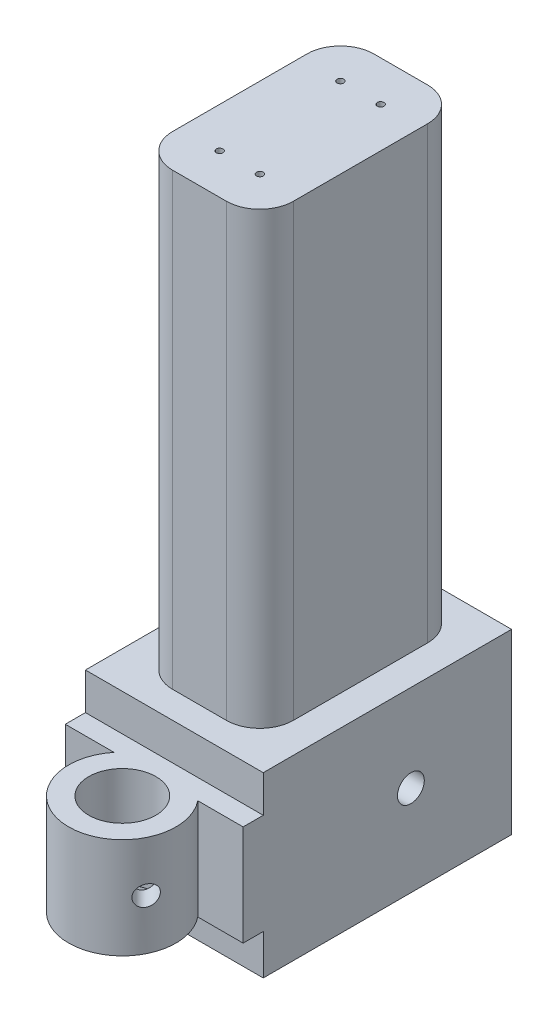
SolidWorks part; units mm, degrees
ref_plane "Plan de face" through (0, 0, 0) normal (0, 0, 1) x (1, 0, 0)
ref_plane "Plan de dessus" through (0, 0, 0) normal (0, 1, 0) x (1, 0, 0)
ref_plane "Plan de droite" through (0, 0, 0) normal (1, 0, 0) x (0, 0, -1)
sketch "Esquisse1" plane through (0, 0, 0) normal (0, 0, 1) x (1, 0, 0)
  line L1 (-12.6964, 11.5945) -> (13.8036, 11.5945)
  line L2 (-12.6964, 11.5945) -> (-12.6964, -14.9055)
  line L3 (-12.6964, -14.9055) -> (13.8036, -14.9055)
  line L4 (13.8036, 11.5945) -> (13.8036, -14.9055)
  dimension "D1" = 26.5
  dimension "D2" = 26.5
extrude "Boss.-Extru.1" add sketch "Esquisse1" along normal blind 40
sketch "Esquisse2" plane through (0, 0, 0) normal (0, 0, -1) x (-1, 0, 0)
  line L0 (-13.8036, -14.9055) -> (-13.8036, 11.5945) construction
  line L1 (-10.8036, 8.5945) -> (9.6964, 8.5945)
  line L2 (-10.8036, 8.5945) -> (-10.8036, -11.9055)
  line L3 (-10.8036, -11.9055) -> (9.6964, -11.9055)
  line L4 (9.6964, 8.5945) -> (9.6964, -11.9055)
  line L5 (-13.8036, 11.5945) -> (12.6964, 11.5945) construction
  dimension "D1" = 20.5
  dimension "D2" = 20.5
  dimension "D3" = 3
  dimension "D4" = 3
extrude "Enlèv. mat.-Extru.1" cut sketch "Esquisse2" against normal blind 21
ref_plane "Plan1" through (0, -1.4055, 0) normal (0, -1, 0) x (-1, 0, 0)
sketch "Esquisse4" plane through (0, -1.4055, 0) normal (0, -1, 0) x (-1, 0, 0)
  line L0 (12.6964, -40) -> (12.6964, 0) construction
  line L1 (-13.8036, -40) -> (12.6964, -40) construction
  circle A0 centre (-0.8036, -45) radius 5
  circle A1 centre (-0.8036, -45) radius 8
  dimension "D2" = 10
  dimension "D4" = 16
  dimension "D1" = 13.5
  dimension "D3" = 5
extrude "Boss.-Extru.3" add sketch "Esquisse4" along normal blind 7.5
extrude "Boss.-Extru.4" add sketch "Esquisse4<4>" against normal blind 7.5
sketch "Esquisse4<4>" plane through (0, -1.4055, 0) normal (0, -1, 0) x (-1, 0, 0) same geometry as "Esquisse4"
sketch "Esquisse8" plane through (0, -14.9055, 0) normal (0, -1, 0) x (1, 0, 0)
  line L0 (13.8036, 40) -> (13.8036, 0) construction
  line L1 (13.8036, 37) -> (-12.6964, 37)
  line L2 (13.8036, 37) -> (13.8036, 40)
  line L3 (13.8036, 40) -> (-12.6964, 40)
  line L4 (-12.6964, 37) -> (-12.6964, 40)
  dimension "D1" = 3
extrude "Enlèv. mat.-Extru.4" cut sketch "Esquisse8" against normal blind 6
sketch "Esquisse9" plane through (0, 11.5945, 0) normal (0, 1, 0) x (1, 0, 0)
  line L0 (-12.6964, -40) -> (-12.6964, 0) construction
  line L1 (-12.6964, -37) -> (13.8036, -37)
  line L2 (-12.6964, -37) -> (-12.6964, -40)
  line L3 (-12.6964, -40) -> (13.8036, -40)
  line L4 (13.8036, -37) -> (13.8036, -40)
  dimension "D1" = 3
ref_plane "Plan2" through (0, 0, 54) normal (0, 0, 1) x (1, 0, 0)
sketch "Esquisse12" plane through (0, 11.5945, 0) normal (0, 1, 0) x (1, 0, 0)
  line L1 (9.3036, -3) -> (-8.6964, -3)
  line L2 (9.3036, -3) -> (9.3036, -33)
  line L3 (9.3036, -33) -> (-8.6964, -33)
  line L4 (-8.6964, -3) -> (-8.6964, -33)
  line L6 (13.8036, 0) -> (-12.6964, 0) construction
  line L8 (13.8036, -40) -> (13.8036, 0) construction
  dimension "D1" = 18
  dimension "D2" = 30
  dimension "D3" = 3
  dimension "D4" = 4.5
extrude "Boss.-Extru.5" add sketch "Esquisse12" along normal blind 67
fillet "Congé1" radius 5 1 edges at (9.3036, 45.0945, 33) type face fillet first side face at (9.3036, 45.0945, 18) second side face at (0.3036, 45.0945, 33)
fillet "Congé2" radius 5 1 edges at (-8.6964, 45.0945, 33) type face fillet first side face at (-2.1964, 45.0945, 33) second side face at (-8.6964, 45.0945, 18)
fillet "Congé3" radius 5 1 edges at (-8.6964, 45.0945, 3) type face fillet first side face at (-8.6964, 45.0945, 15.5) second side face at (0.3036, 45.0945, 3)
fillet "Congé4" radius 5 1 edges at (9.3036, 45.0945, 3) type face fillet first side face at (9.3036, 45.0945, 15.5) second side face at (2.8036, 45.0945, 3)
sketch "Esquisse13" plane through (0, 78.5945, 0) normal (0, 1, 0) x (1, 0, 0)
  line L0 (4.3036, -3) -> (-3.6964, -3) construction
  line L1 (9.3036, -28) -> (9.3036, -8) construction
  line L2 (4.3036, -3) -> (-3.6964, -3) construction
  line L3 (-8.6964, -8) -> (-8.6964, -28) construction
  line L4 (-3.6964, -33) -> (4.3036, -33) construction
  circle A0 centre (3.3036, -9) radius 0.5
  circle A1 centre (-2.6964, -9) radius 0.5
  circle A2 centre (3.3036, -27) radius 0.5
  circle A3 centre (-2.6964, -27) radius 0.5
  dimension "D1" = 1
  dimension "D2" = 1
  dimension "D3" = 1
  dimension "D4" = 1
  dimension "D5" = 6
  dimension "D6" = 6
  dimension "D7" = 6
  dimension "D8" = 6
  dimension "D9" = 6
  dimension "D10" = 6
  dimension "D11" = 6
  dimension "D12" = 6
ref_plane "Plan13" through (0, 0, 51) normal (0, 0, 1) x (1, 0, 0)
ref_plane "Plan14" through (13.6518, 0, 13.6518) normal (-0.7071, 0, -0.7071) x (-0.7071, 0, 0.7071)
ref_plane "Plan15" through (28.5587, 0, 28.5587) normal (0.7071, 0, 0.7071) x (0.7071, 0, -0.7071)
ref_plane "Plan16" through (-13.0982, 0, 13.0982) normal (-0.7071, 0, 0.7071) x (0.7071, 0, 0.7071)
ref_plane "Plan17" through (-27.755, 0, 27.755) normal (-0.7071, 0, 0.7071) x (0.7071, 0, 0.7071)
sketch "Esquisse17" plane through (28.5587, 0, 28.5587) normal (0.7071, 0, 0.7071) x (0.7071, 0, -0.7071)
  line L1 (-35.1406, -14.9055) -> (-16.4023, -14.9055) construction
  circle A0 centre (-28.739, -1.4055) radius 1.5
  dimension "D1" = 3
  dimension "D2" = 13.5
sketch "Esquisse18" plane through (-27.755, 0, 27.755) normal (-0.7071, 0, 0.7071) x (0.7071, 0, 0.7071)
  line L1 (17.1853, -14.9055) -> (35.9236, -14.9055) construction
  circle A0 centre (29.8754, -1.4055) radius 1.5
  dimension "D1" = 3
  dimension "D2" = 13.5
extrude "Enlèv. mat.-Extru.7" cut sketch "Esquisse17" against normal up to next
extrude "Enlèv. mat.-Extru.8" cut sketch "Esquisse18" against normal up to next
extrude "Enlèv. mat.-Extru.9" cut sketch "Esquisse13" against normal blind 5
sketch "Esquisse19" plane through (-12.6964, 0, 0) normal (-1, 0, 0) x (0, 0, 1)
  line L0 (37, -14.9055) -> (0, -14.9055) construction
  line L1 (0, 11.5945) -> (0, -14.9055) construction
  circle A0 centre (15, -1.4055) radius 2
  dimension "D2" = 4
  dimension "D1" = 13.5
  dimension "D3" = 15
extrude "Enlèv. mat.-Extru.10" cut sketch "Esquisse19" against normal through all both and the other way through all
sketch "Esquisse20" plane through (0, -14.9055, 0) normal (0, -1, 0) x (1, 0, 0)
  line L0 (13.8036, 37) -> (13.8036, 0) construction
  line L1 (-12.6964, 0) -> (13.8036, 0) construction
  circle A0 centre (0.3036, 15) radius 2
  dimension "D3" = 4
  dimension "D1" = 13.5
  dimension "D2" = 15
extrude "Enlèv. mat.-Extru.11" cut sketch "Esquisse20" against normal up to next
extrude "Enlèv. mat.-Extru.13" cut sketch "Esquisse9" against normal blind 5.5
